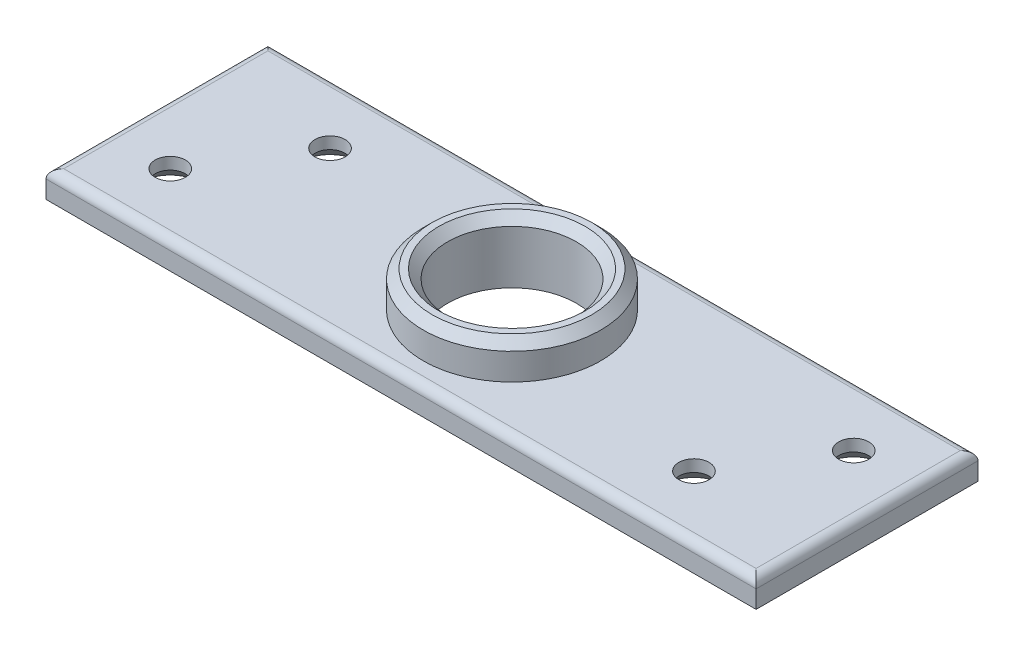
SolidWorks part; units mm, degrees
material "Aço cromo inoxidável"
ref_plane "Plano frontal" through (0, 0, 0) normal (0, 0, 1) x (1, 0, 0)
ref_plane "Plano superior" through (0, 0, 0) normal (0, 1, 0) x (1, 0, 0)
ref_plane "Plano direito" through (0, 0, 0) normal (1, 0, 0) x (0, 0, -1)
other "Caixa delimitadora"
ref_plane "Default Plane" through (-40, -1.5, 12.5) normal (0, 0, -1) x (-1, 0, 0)
sketch "Esboço1" plane through (0, 0, 0) normal (0, 1, 0) x (1, 0, 0)
  line L1 (-40, -12.5) -> (40, -12.5)
  line L2 (-40, -12.5) -> (-40, 12.5)
  line L3 (-40, 12.5) -> (40, 12.5)
  line L4 (40, -12.5) -> (40, 12.5)
  line L5 (-40, -12.5) -> (40, 12.5) construction
  line L6 (-40, 12.5) -> (40, -12.5) construction
  circle A0 centre (0, 0) radius 10
  point P0 (0, 0)
  dimension "D3" = 20
  dimension "D1" = 80
  dimension "D2" = 25
extrude "Ressalto-extrusão1" add sketch "Esboço1" along normal mid plane 3
sketch "Esboço2" plane through (0, -1.5, 0) normal (0, -1, 0) x (1, 0, 0)
  circle A0 centre (0, 0) radius 10 construction
  circle A1 centre (0, 0) radius 10
  circle A2 centre (0, 0) radius 7.25
  dimension "D1" = 2.75
extrude "Ressalto-extrusão2" add sketch "Esboço2" against normal offset from surface (7 mm away) 4 separate body up to face at (0, 1.5, 0) offset beyond the face yes
chamfer "Chanfro1" distance 1 angle 45 2 edges at (0, 5.5, -7.25) (0, 5.5, -10)
fillet "Filete1" radius 1 4 edges at (-40, 1.5, 0) (0, 1.5, -12.5) (40, 1.5, 0) (0, 1.5, 12.5)
sketch "Esboço3" plane through (0, -1.5, 0) normal (0, -1, 0) x (-1, 0, 0)
  point P0 (26, 5.5)
  point P1 (33, -5.5)
  point P3 (-26, -5.5)
  point P5 (-33, 5.5)
  dimension "D1" = 26
  dimension "D2" = 33
  dimension "D3" = 26
  dimension "D4" = 33
  dimension "D5" = 5.5
  dimension "D6" = 5.5
hole_wizard "Escareado para SFHCS M31" positions "Esboço4" profile "Esboço5" countersink size "M3" standard "Ansi Metric" end condition through all
sketch "Esboço4" plane through (0, -1.5, 0) normal (0, -1, 0) x (-1, 0, 0)
  point P0 (-33, 5.5)
  point P3 (-26, -5.5)
  point P6 (26, 5.5)
  point P9 (33, -5.5)
sketch "Esboço5" plane through (33, -1.5, -5.5) normal (1, 0, 0) x (0, 0, -1)
  line L0 (0, 0) -> (0, 7)
  line L1 (0, 7) -> (1.7, 7)
  line L2 (1.7, 7) -> (1.7, 1.66)
  line L3 (1.7, 1.66) -> (3.36, 0)
  line L5 (3.36, 0) -> (0, 0)
  line L6 (-1.7, 1.66) -> (-3.36, 0) construction
  line L11 (0, -6.35) -> (0, 107.95) construction
  dimension "Thru Hole Dia." = 3.4
  dimension "Thru Hole Depth" = 7
  dimension "Near C'Sink Dia." = 6.72
  dimension "Near C'Sink Angle" = 90
